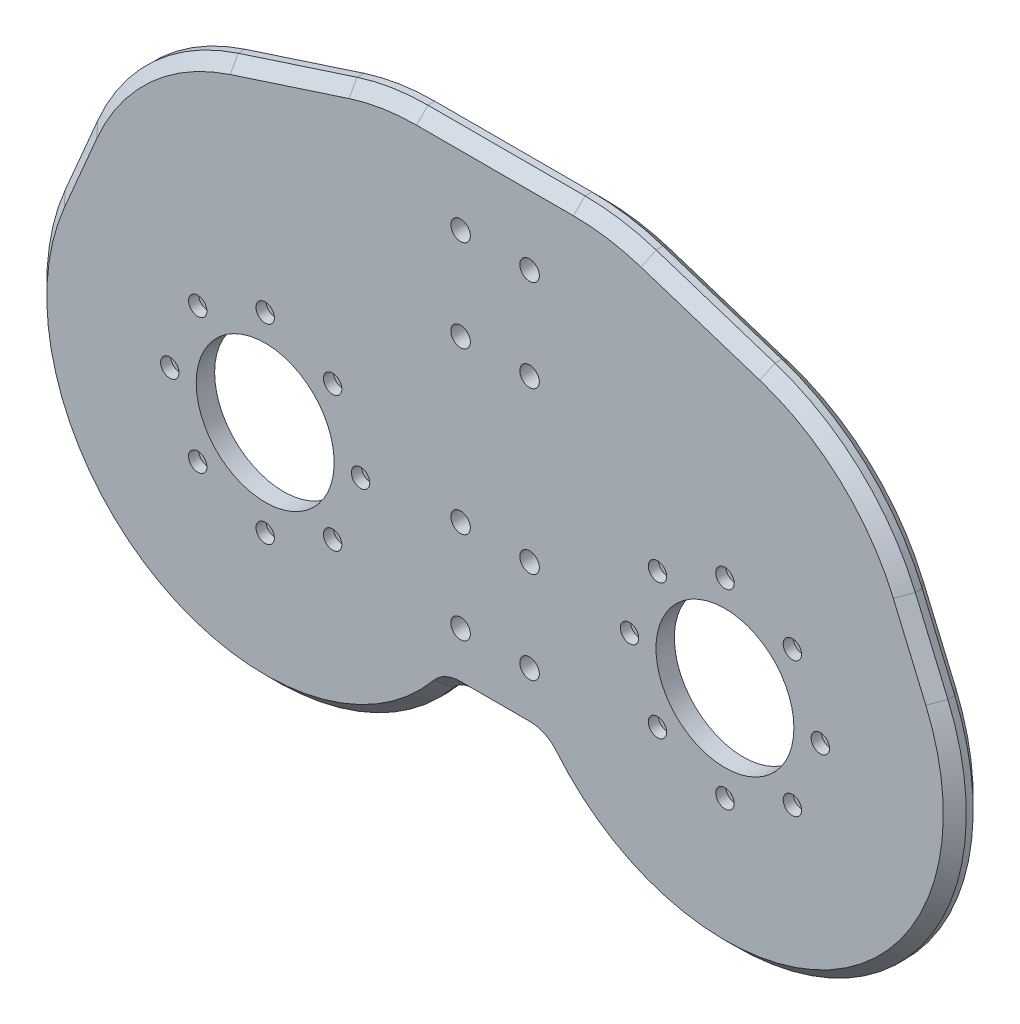
SolidWorks part; units mm, degrees
material "6061 合金"
ref_plane "前视基准面" through (0, 0, 0) normal (0, 0, 1) x (1, 0, 0)
ref_plane "上视基准面" through (0, 0, 0) normal (0, 1, 0) x (1, 0, 0)
ref_plane "右视基准面" through (0, 0, 0) normal (1, 0, 0) x (0, 0, -1)
other "Configuration Table"
sketch "草图1" plane through (0, 0, 0) normal (0, 0, 1) x (1, 0, 0)
  line L0 (0, 0) -> (0, 250) construction
  line L1 (0, 250) -> (769.4209, 0)
  line L3 (769.4209, 0) -> (0, 0)
  line L4 (-50, 404.7785) -> (-50, -103.66) construction
  line L5 (-869.4209, 0) -> (-100, 0)
  line L6 (-100, 250) -> (-869.4209, 0)
  line L7 (-100, 0) -> (-100, 250) construction
  line L8 (-100, 250) -> (0, 250)
  line L9 (-100, 0) -> (0, 0)
  circle A0 centre (50, 100) radius 85 construction
  circle A1 centre (50, 100) radius 30
  circle A2 centre (-150, 100) radius 85 construction
  circle A3 centre (-150, 100) radius 30
  dimension "D1" = 170
  dimension "D4" = 60
  dimension "D2" = 100
  dimension "D3" = 72
  dimension "D5" = 250
  dimension "D6" = 100
  dimension "D7" = 50
extrude "凸台-拉伸1" add sketch "草图1" along normal blind 8
sketch "草图8" plane through (0, 0, 8) normal (0, 0, 1) x (1, 0, 0)
  line L0 (50, 100) -> (50, 171.8517) construction
  line L1 (-50, 311.6242) -> (-50, -58.5513) construction
  line L2 (-150, 100) -> (-150, 171.8517) construction
  circle A0 centre (50, 100) radius 41.5 construction
  circle A1 centre (50, 141.5) radius 2.25
  circle A2 centre (79.3449, 129.3449) radius 2.25
  circle A3 centre (91.5, 100) radius 2.25
  circle A4 centre (79.3449, 70.6551) radius 2.25
  circle A5 centre (50, 58.5) radius 2.25
  circle A6 centre (20.6551, 70.6551) radius 2.25
  circle A7 centre (8.5, 100) radius 2.25
  circle A8 centre (20.6551, 129.3449) radius 2.25
  circle A9 centre (50, 100) radius 30 construction
  circle A10 centre (-150, 100) radius 30 construction
  circle A11 centre (-150, 100) radius 41.5 construction
  circle A12 centre (-120.6551, 129.3449) radius 2.25
  circle A13 centre (-108.5, 100) radius 2.25
  circle A14 centre (-120.6551, 70.6551) radius 2.25
  circle A15 centre (-150, 58.5) radius 2.25
  circle A16 centre (-179.3449, 70.6551) radius 2.25
  circle A17 centre (-191.5, 100) radius 2.25
  circle A18 centre (-179.3449, 129.3449) radius 2.25
  circle A19 centre (-150, 141.5) radius 2.25
  point P22 (50, 100)
  point P46 (-150, 100)
  dimension "D1" = 83
  dimension "D2" = 4.5
  dimension "D3" = 8
extrude "切除-拉伸5" cut sketch "草图8" against normal through all both and the other way through all
sketch "草图9" plane through (0, 0, 8) normal (0, 0, 1) x (1, 0, 0)
  line L0 (-50, 330.1155) -> (-50, -36.3961) construction
  circle A0 centre (-150, 100) radius 41.5 construction
  circle A1 centre (-150, 141.5) radius 4
  circle A2 centre (-120.6551, 129.3449) radius 4
  circle A3 centre (-108.5, 100) radius 4
  circle A4 centre (-120.6551, 70.6551) radius 4
  circle A5 centre (-150, 58.5) radius 4
  circle A6 centre (-179.3449, 70.6551) radius 4
  circle A7 centre (-191.5, 100) radius 4
  circle A8 centre (-179.3449, 129.3449) radius 4
  circle A9 centre (50, 100) radius 30 construction
  circle A10 centre (-150, 100) radius 30 construction
  circle A11 centre (50, 100) radius 41.5 construction
  circle A12 centre (79.3449, 129.3449) radius 4
  circle A13 centre (91.5, 100) radius 4
  circle A14 centre (79.3449, 70.6551) radius 4
  circle A15 centre (50, 58.5) radius 4
  circle A16 centre (20.6551, 70.6551) radius 4
  circle A17 centre (8.5, 100) radius 4
  circle A18 centre (20.6551, 129.3449) radius 4
  circle A19 centre (50, 141.5) radius 4
  point P22 (-150, 100)
  point P45 (50, 100)
  dimension "D1" = 8
  dimension "D2" = 8
extrude "切除-拉伸6" cut sketch "草图9" against normal blind 4.4
fillet "圆角1" radius 100 2 edges at (-869.4209, 0, 4) (769.4209, 0, 4)
sketch "草图12" plane through (0, 0, 0) normal (0, 0, -1) x (-1, 0, 0)
  line L0 (50, 285.9765) -> (50, -67.6003) construction
  line L1 (238.0457, 0) -> (-138.0457, 0) construction
  line L3 (30, 40) -> (70, 40)
  line L6 (150, 0) -> (-50, 0)
  arc A0 (70, 40) -> (150, 0) centre (150, 100) ccw
  circle A2 centre (150, 100) radius 30 construction
  circle A3 centre (-50, 100) radius 30 construction
  arc A7 (-50, 0) -> (30, 40) centre (-50, 100) ccw
  dimension "D1" = 40
extrude "切除-拉伸7" cut sketch "草图12" against normal blind 83
sketch "草图13" plane through (0, 0, 8) normal (0, 0, 1) x (1, 0, 0)
  line L0 (-238.0457, 0) -> (-150, 0) construction
  line L1 (-238.0457, 0) -> (-150, 0)
  line L2 (-50, 304.265) -> (-50, -26.0703) construction
  line L3 (-210, 214.2588) -> (-241.9905, 139.2142)
  line L4 (-100, 250) -> (-268.9474, 195.1057) construction
  line L5 (-210, 214.2588) -> (-268.9474, 195.1057)
  line L6 (110, 214.2588) -> (168.9474, 195.1057)
  line L7 (110, 214.2588) -> (141.9905, 139.2142)
  line L8 (138.0457, 0) -> (50, 0)
  arc A0 (-241.9905, 139.2142) -> (-150, 0) centre (-150, 100) ccw
  circle A1 centre (50, 100) radius 30 construction
  circle A2 centre (-150, 100) radius 30 construction
  arc A3 (-268.9474, 195.1057) -> (-238.0457, 0) centre (-238.0457, 100) ccw construction
  arc A4 (-268.9474, 195.1057) -> (-238.0457, 0) centre (-238.0457, 100) ccw
  arc A5 (168.9474, 195.1057) -> (138.0457, 0) centre (138.0457, 100) cw
  arc A6 (141.9905, 139.2142) -> (50, 0) centre (50, 100) cw
  dimension "D1" = 160
extrude "切除-拉伸8" cut sketch "草图13" against normal blind 83
fillet "圆角3" radius 100 4 edges at (110, 214.2588, 4) (0, 250, 4) (-100, 250, 4) (-210, 214.2588, 4)
fillet "圆角4" radius 10 2 edges at (-30, 40, 4) (-70, 40, 4)
sketch "草图14" plane through (0, 0, 8) normal (0, 0, 1) x (1, 0, 0)
  line L0 (-50, 283.8941) -> (-50, -28.6031) construction
  line L1 (-65.1472, 40) -> (-34.8528, 40) construction
  circle A0 centre (-150, 100) radius 30 construction
  circle A1 centre (50, 100) radius 30 construction
  circle A2 centre (-35, 65) radius 4.25
  circle A3 centre (-35, 105) radius 4.25
  circle A4 centre (-35, 175) radius 4.25
  circle A5 centre (-35, 215) radius 4.25
  circle A6 centre (-65, 215) radius 4.25
  circle A7 centre (-65, 175) radius 4.25
  circle A8 centre (-65, 105) radius 4.25
  circle A9 centre (-65, 65) radius 4.25
  dimension "D6" = 8.5
  dimension "D1" = 40
  dimension "D2" = 15
  dimension "D3" = 40
  dimension "D4" = 70
  dimension "D5" = 15
  dimension "D7" = 25
extrude "切除-拉伸9" cut sketch "草图14" against normal blind 83
sketch "草图15" plane through (0, 0, 0) normal (0, 0, -1) x (-1, 0, 0)
  line L0 (50, 291.1692) -> (50, -23.3122) construction
  line L1 (55, 50) -> (78.193, 50)
  line L2 (55, 240) -> (98.4162, 240)
  line L3 (98.4162, 240) -> (199.4298, 207.1787)
  line L4 (199.4298, 207.1787) -> (230.4916, 134.3125)
  line L5 (65.1472, 40) -> (34.8528, 40) construction
  line L6 (15.8384, 250) -> (84.1616, 250) construction
  line L7 (115.0633, 245.1057) -> (166.7459, 228.3129) construction
  line L8 (227.8347, 172.4215) -> (241.9905, 139.2142) construction
  line L9 (55, 240) -> (55, 50)
  line L10 (45, 240) -> (45, 50)
  line L11 (-99.4298, 207.1787) -> (-130.4916, 134.3125)
  line L12 (1.5838, 240) -> (-99.4298, 207.1787)
  line L13 (45, 240) -> (1.5838, 240)
  line L14 (45, 50) -> (21.807, 50)
  line L21 (-15.0633, 245.1057) -> (-66.7459, 228.3129)
  line L22 (-127.8347, 172.4215) -> (-141.9905, 139.2142)
  line L23 (34.8528, 40) -> (65.1472, 40)
  line L24 (241.9905, 139.2142) -> (227.8347, 172.4215)
  line L25 (166.7459, 228.3129) -> (115.0633, 245.1057)
  line L26 (84.1616, 250) -> (15.8384, 250)
  line L27 (-15.0633, 245.1057) -> (-66.7459, 228.3129)
  line L28 (-127.8347, 172.4215) -> (-141.9905, 139.2142)
  line L29 (34.8528, 40) -> (65.1472, 40)
  line L30 (241.9905, 139.2142) -> (227.8347, 172.4215)
  line L31 (166.7459, 228.3129) -> (115.0633, 245.1057)
  line L32 (84.1616, 250) -> (15.8384, 250)
  circle A0 centre (150, 100) radius 87.5 construction
  circle A1 centre (150, 100) radius 30 construction
  circle A2 centre (-50, 100) radius 30 construction
  arc A3 (78.193, 50) -> (230.4916, 134.3125) centre (150, 100) ccw
  circle A4 centre (-50, 100) radius 87.5 construction
  arc A5 (21.807, 50) -> (-130.4916, 134.3125) centre (-50, 100) cw
  arc A14 (-66.7459, 228.3129) -> (-127.8347, 172.4215) centre (-35.8442, 133.2073) ccw
  arc A15 (-141.9905, 139.2142) -> (27.1389, 36.3636) centre (-50, 100) ccw
  arc A16 (34.8528, 40) -> (27.1389, 36.3636) centre (34.8528, 30) ccw
  arc A17 (72.8611, 36.3636) -> (65.1472, 40) centre (65.1472, 30) ccw
  arc A18 (72.8611, 36.3636) -> (241.9905, 139.2142) centre (150, 100) ccw
  arc A19 (227.8347, 172.4215) -> (166.7459, 228.3129) centre (135.8442, 133.2073) ccw
  arc A20 (115.0633, 245.1057) -> (84.1616, 250) centre (84.1616, 150) ccw
  arc A21 (15.8384, 250) -> (-15.0633, 245.1057) centre (15.8384, 150) ccw
  arc A22 (-66.7459, 228.3129) -> (-127.8347, 172.4215) centre (-35.8442, 133.2073) ccw
  arc A23 (-141.9905, 139.2142) -> (27.1389, 36.3636) centre (-50, 100) ccw
  arc A24 (34.8528, 40) -> (27.1389, 36.3636) centre (34.8528, 30) ccw
  arc A25 (72.8611, 36.3636) -> (65.1472, 40) centre (65.1472, 30) ccw
  arc A26 (72.8611, 36.3636) -> (241.9905, 139.2142) centre (150, 100) ccw
  arc A27 (227.8347, 172.4215) -> (166.7459, 228.3129) centre (135.8442, 133.2073) ccw
  arc A28 (115.0633, 245.1057) -> (84.1616, 250) centre (84.1616, 150) ccw
  arc A29 (15.8384, 250) -> (-15.0633, 245.1057) centre (15.8384, 150) ccw
  dimension "D1" = 175
  dimension "D2" = 10
  dimension "D3" = 10
  dimension "D4" = 10
  dimension "D5" = 5
  dimension "D6" = 0
extrude "凸台-拉伸2" add sketch "草图15" along normal blind 5
fillet "圆角6" radius 100 2 edges at (-199.4298, 207.1787, -2.5) (99.4298, 207.1787, -2.5)
fillet "圆角7" radius 10 8 edges at (-21.807, 50, -2.5) (-45, 50, -2.5) (-55, 50, -2.5) (-78.193, 50, -2.5) (-98.4162, 240, -2.5) (-55, 240, -2.5) (-1.5838, 240, -2.5) (-45, 240, -2.5)
sketch "草图16" plane through (0, 0, 0) normal (0, 0, -1) x (-1, 0, 0)
  line L0 (80, 230) -> (80, 130)
  line L1 (80, 130) -> (166.6025, 180)
  line L2 (166.6025, 180) -> (80, 230)
  line L3 (50, 302.4124) -> (50, -31.91) construction
  line L4 (84.1616, 250) -> (15.8384, 250) construction
  line L5 (-66.6025, 180) -> (20, 230)
  line L6 (20, 130) -> (-66.6025, 180)
  line L7 (20, 230) -> (20, 130)
  circle A0 centre (150, 100) radius 30 construction
  circle A1 centre (-50, 100) radius 30 construction
  dimension "D1" = 30
  dimension "D2" = 20
  dimension "D3" = 100
  dimension "D4" = 100
  dimension "D5" = 100
extrude "切除-拉伸10" [suppressed] cut sketch "草图16" against normal blind 69
fillet "圆角5" [suppressed] radius 10
chamfer "倒角1" distance 5 angle 45 28 edges at (-69.4112, 39.0453, 8) (-50, 40, 8) (-201.9587, 14.5582, 8) (-30.5888, 39.0453, 8) (-234.9126, 155.8179, 8) (101.9587, 14.5582, 8) (-203.3467, 206.9868, 8) (134.9126, 155.8179, 8) (-140.9046, 236.7093, 8) (103.3467, 206.9868, 8) (-99.805, 248.7688, 8) (40.9046, 236.7093, 8) (-50, 250, 8) (-0.195, 248.7688, 8) (-50, 40, -5) (-69.4112, 39.0453, -5) (-30.5888, 39.0453, -5) (-201.9587, 14.5582, -5) (101.9587, 14.5582, -5) (-234.9126, 155.8179, -5) (134.9126, 155.8179, -5) (-203.3467, 206.9868, -5) (103.3467, 206.9868, -5) (-140.9046, 236.7093, -5) (40.9046, 236.7093, -5) (-99.805, 248.7688, -5) (-0.195, 248.7688, -5) (-50, 250, -5)
chamfer "倒角2" [suppressed] distance 5 angle 45
